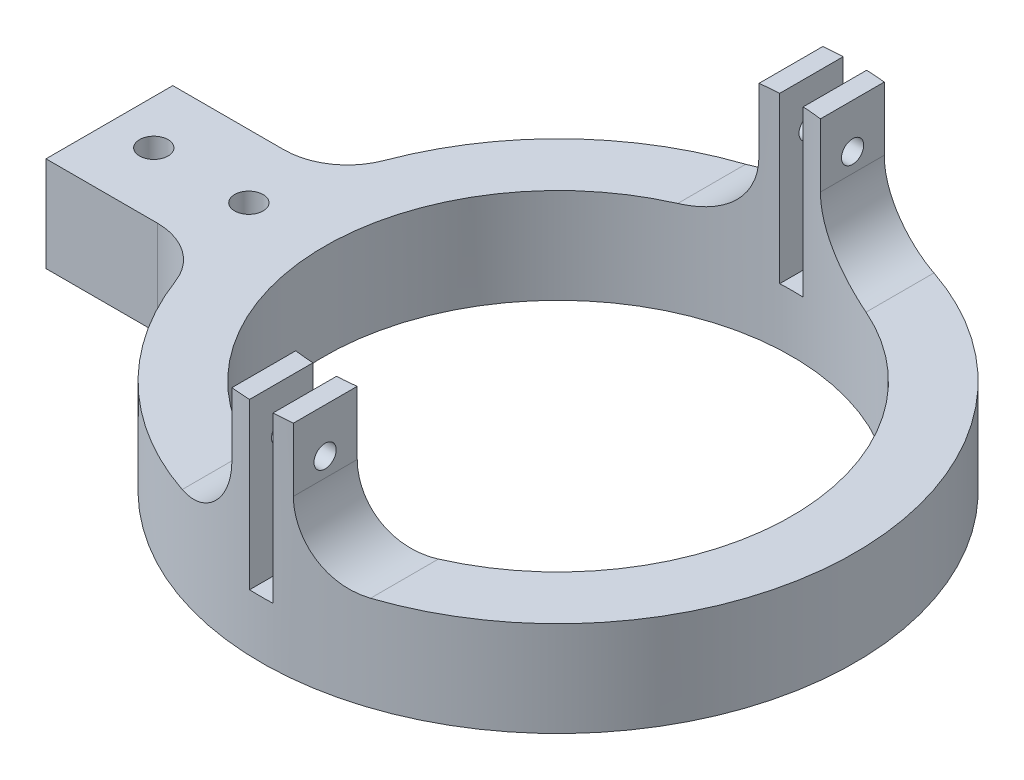
SolidWorks part; units mm, degrees
ref_plane "Front Plane" through (0, 0, 0) normal (0, 0, 1) x (1, 0, 0)
ref_plane "Top Plane" through (0, 0, 0) normal (0, 1, 0) x (1, 0, 0)
ref_plane "Right Plane" through (0, 0, 0) normal (1, 0, 0) x (0, 0, -1)
sketch "Sketch1" plane through (0, 0, 0) normal (0, 1, 0) x (1, 0, 0)
  line L0 (-97.4451, 0) -> (50.4854, 0) construction
  line L2 (-70.7703, -10) -> (-45.7703, -10)
  line L3 (-70.7703, -10) -> (-70.7703, 10)
  line L4 (-70.7703, 10) -> (-45.7703, 10)
  line L6 (-70.7703, -10) -> (-45.7703, 10) construction
  line L7 (-70.7703, 10) -> (-45.7703, -10) construction
  circle A0 centre (0, 0) radius 36.85
  arc A1 (-45.7703, -10) -> (-45.7703, 10) centre (0, 0) ccw
  circle A2 centre (0, 0) radius 46.85 construction
  point P8 (-58.2703, 0)
  dimension "D1" = 73.7
  dimension "D3" = 20
  dimension "D4" = 25
  dimension "D2" = 10
extrude "Boss-Extrude1" add sketch "Sketch1" along normal blind 15
sketch "Sketch2" plane through (0, 15, 0) normal (0, 1, 0) x (1, 0, 0)
  line L0 (-70.7703, 0) -> (-36.85, 0) construction
  line L1 (-70.7703, 10) -> (-70.7703, -10) construction
  circle A0 centre (0, 0) radius 36.85 construction
  circle A1 centre (-63.7703, 0) radius 2.25
  circle A2 centre (-48.7703, 0) radius 2.25
  dimension "D1" = 4.5
  dimension "D2" = 4.5
  dimension "D3" = 7
  dimension "D4" = 15
extrude "Cut-Extrude1" cut sketch "Sketch2" against normal through all
sketch "Sketch3" plane through (0, 15, 0) normal (0, 1, 0) x (1, 0, 0)
  line L0 (0, 46.85) -> (0, -46.85) construction
  line L1 (-1.85, 46.8135) -> (-1.85, 36.8035)
  line L2 (-4.85, 46.5983) -> (-4.85, 36.5294)
  line L3 (4.85, 46.5983) -> (4.85, 36.5294)
  line L4 (1.85, 46.8135) -> (1.85, 36.8035)
  line L5 (-70.7703, 0) -> (46.85, 0) construction
  line L6 (-70.7703, 10) -> (-70.7703, -10) construction
  line L7 (4.85, -46.5983) -> (4.85, -36.5294)
  line L8 (1.85, -46.8135) -> (1.85, -36.8035)
  line L9 (-1.85, -46.8135) -> (-1.85, -36.8035)
  line L10 (-4.85, -46.5983) -> (-4.85, -36.5294)
  arc A0 (-45.7703, -10) -> (-45.7703, 10) centre (0, 0) ccw construction
  circle A1 centre (0, 0) radius 36.85 construction
  arc A2 (1.85, -36.8035) -> (4.85, -36.5294) centre (0, 0) ccw
  arc A3 (-4.85, -36.5294) -> (-1.85, -36.8035) centre (0, 0) ccw
  arc A4 (4.85, 36.5294) -> (1.85, 36.8035) centre (0, 0) ccw
  arc A5 (4.85, 46.5983) -> (1.85, 46.8135) centre (0, 0) ccw
  arc A6 (-1.85, 46.8135) -> (-4.85, 46.5983) centre (0, 0) ccw
  arc A7 (-1.85, 36.8035) -> (-4.85, 36.5294) centre (0, 0) ccw
  arc A8 (-4.85, -46.5983) -> (-1.85, -46.8135) centre (0, 0) ccw
  arc A9 (1.85, -46.8135) -> (4.85, -46.5983) centre (0, 0) ccw
  arc A10 (46.85, 0) -> (-45.7703, 10) centre (0, 0) ccw
  arc M9 (-45.7703, -10) -> (-45.7703, 10) centre (0, 0) ccw
  circle M13 centre (0, 0) radius 36.85
  dimension "D1" = 3.7
  dimension "D2" = 3
extrude "Boss-Extrude2" add sketch "Sketch3" along normal blind 20 contours L10 L9 M9 M13 | L8 L7 M9 M13 | L4 L3 M9 M13 | L2 L1 M9 M13 region at (-3.3515, 15, -41.7044) region at (3.3515, 15, -41.7044) region at (-3.3515, 15, 41.7044) region at (3.3515, 15, 41.7044)
fillet "Fillet1" radius 10 4 edges at (4.85, 15, 41.5639) (-4.85, 15, 41.5639) (-4.85, 15, -41.5639) (4.85, 15, -41.5639)
sketch "Sketch4" plane through (0, 15, 0) normal (0, 1, 0) x (1, 0, 0)
  line L0 (-1.85, 46.8135) -> (-1.85, 36.8035) construction
  line L1 (1.85, 36.8035) -> (1.85, 46.8135) construction
  line L2 (1.85, -46.8135) -> (1.85, -36.8035) construction
  line L3 (-1.85, -36.8035) -> (-1.85, -46.8135) construction
  line L4 (-1.85, 46.8135) -> (-1.85, 36.8035)
  line L5 (1.85, 36.8035) -> (1.85, 46.8135)
  line L6 (1.85, -46.8135) -> (1.85, -36.8035)
  line L7 (-1.85, -36.8035) -> (-1.85, -46.8135)
  arc A0 (1.85, 36.8035) -> (-1.85, 36.8035) centre (0, 0) ccw construction
  arc A1 (1.85, 46.8135) -> (-1.85, 46.8135) centre (0, 0) ccw construction
  arc A2 (-1.85, -36.8035) -> (1.85, -36.8035) centre (0, 0) ccw construction
  arc A3 (-1.85, -46.8135) -> (1.85, -46.8135) centre (0, 0) ccw construction
  arc A4 (1.85, 36.8035) -> (-1.85, 36.8035) centre (0, 0) ccw
  arc A5 (1.85, 46.8135) -> (-1.85, 46.8135) centre (0, 0) ccw
  arc A6 (-1.85, -36.8035) -> (1.85, -36.8035) centre (0, 0) ccw
  arc A7 (-1.85, -46.8135) -> (1.85, -46.8135) centre (0, 0) ccw
extrude "Cut-Extrude2" cut sketch "Sketch4" against normal blind 6
sketch "Sketch5" plane through (0, 0, 0) normal (1, 0, 0) x (0, 0, -1)
  line L0 (0, 0) -> (0, 45.4601) construction
  line L1 (-48.739, 28) -> (49.7163, 28) construction
  line L2 (-41.6, 41.9757) -> (-41.6, -3.4488) construction
  line L3 (-46.85, 0) -> (46.85, 0) construction
  circle A0 centre (-41.6, 28) radius 1.75
  dimension "D2" = 3.5
  dimension "D1" = 41.6
  dimension "D3" = 28
extrude "Cut-Extrude3" cut sketch "Sketch5" against normal through all both and the other way through all
fillet "Fillet2" radius 10 2 edges at (-45.7703, 7.5, -10) (-45.7703, 7.5, 10)
mirror "Mirror1" about plane through (0, 0, 0) normal (0, 0, 1) of "Cut-Extrude3"
